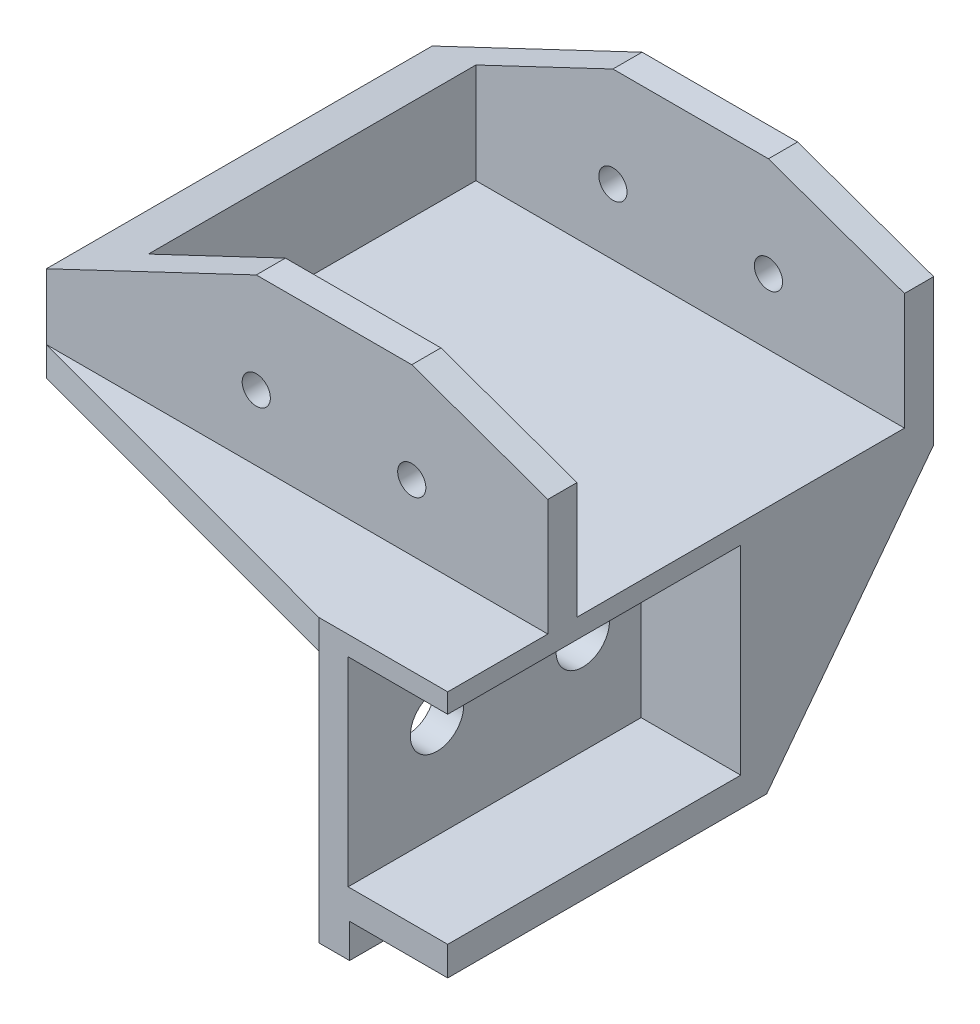
SolidWorks part; units mm, degrees
ref_plane "前视基准面" through (0, 0, 0) normal (0, 0, 1) x (1, 0, 0)
ref_plane "上视基准面" through (0, 0, 0) normal (0, 1, 0) x (1, 0, 0)
ref_plane "右视基准面" through (0, 0, 0) normal (1, 0, 0) x (0, 0, -1)
sketch "草图1" plane through (0, 0, 0) normal (0, 0, 1) x (1, 0, 0)
  line L0 (0, 0) -> (-103.2, 0)
  line L1 (-103.2, 0) -> (-103.2, 20)
  line L2 (-103.2, 20) -> (0, 20)
  line L3 (0, 20) -> (0, 0)
  dimension "D1" = 103.2
  dimension "D2" = 20
extrude "凸台-拉伸1" add sketch "草图1" along normal blind 39.7
sketch "草图2" plane through (0, 20, 0) normal (0, 1, 0) x (1, 0, 0)
  line L0 (-51.6, 0) -> (-51.6, -39.7) construction
  line L2 (-99.2, -19.85) -> (-72.6862, -19.85) construction
  line L5 (-95.7, -3) -> (-7.5, -3)
  line L6 (-95.7, -3) -> (-95.7, -36.7)
  line L7 (-95.7, -36.7) -> (-7.5, -36.7)
  line L8 (-7.5, -3) -> (-7.5, -36.7)
  dimension "D1" = 88.2
  dimension "D2" = 33.7
extrude "切除-拉伸1" cut sketch "草图2" against normal offset from surface (17 mm away) 3 up to face at (-51.6, 0, 19.85)
sketch "草图3" plane through (0, 0, 0) normal (0, -1, 0) x (1, 0, 0)
  line L6 (-51.6, 39.7) -> (-51.6, -13.7739) construction
  line L11 (-103.2, 0) -> (0, 0) construction
  line L12 (-64.85, 0) -> (-38.35, 0)
  line L15 (-64.85, 0) -> (-64.85, 50)
  line L16 (-64.85, 50) -> (-38.35, 50)
  line L17 (-38.35, 50) -> (-38.35, 0)
  point P11 (-51.6, 0)
  dimension "D1" = 50
  dimension "D2" = 13.25
extrude "凸台-拉伸2" add sketch "草图3" along normal blind 29 from offset 3 offset against normal yes
sketch "草图21" plane through (0, 0, 50) normal (0, 0, 1) x (1, 0, 0)
  line L0 (-7.5, 3) -> (-95.7, 3) construction
  line L1 (-7.5, 3) -> (-95.7, 3) construction
  line L2 (-98.033, -9.25) -> (-9.0097, -9.25) construction
  line L3 (-51.6, -26) -> (-51.6, 30.6239) construction
  line L4 (-61.85, 1) -> (-41.35, 1)
  line L5 (-61.85, 1) -> (-61.85, -19.5)
  line L6 (-61.85, -19.5) -> (-41.35, -19.5)
  line L7 (-41.35, 1) -> (-41.35, -19.5)
  dimension "D1" = 12.25
  dimension "D2" = 20.5
  dimension "D3" = 20.5
extrude "切除-拉伸11" cut sketch "草图21" against normal offset from surface (30.15 mm away) 19.85 up to face at (-51.6, -1.5, 0)
sketch "草图22" plane through (0, -26, 0) normal (0, -1, 0) x (1, 0, 0)
  line L1 (-61.7, 50) -> (-41.5, 50)
  line L2 (-41.5, 50) -> (-41.5, 0)
  line L3 (-64.85, 0) -> (-38.35, 0) construction
  line L4 (-41.5, 0) -> (-61.7, 0)
  line L5 (-61.7, 0) -> (-61.7, 50)
  line L6 (-38.35, 50) -> (-64.85, 50) construction
  dimension "D1" = 0
extrude "切除-拉伸12" cut sketch "草图22" against normal offset from surface (3.5 mm away) 3 up to face at (-51.6, -19.5, 34.925)
sketch "草图24" plane through (-38.35, 0, 0) normal (1, 0, 0) x (0, 0, -1)
  line L0 (0, 0) -> (0, -26)
  line L1 (0, -26) -> (-19.85, -26)
  line L2 (0, -26) -> (-50, -26) construction
  line L3 (-19.85, -26) -> (0, 0)
  line L4 (-19.85, -19.5) -> (-19.85, 1) construction
  line L5 (-19.85, -19.5) -> (-19.85, 1) construction
extrude "切除-拉伸14" cut sketch "草图24" against normal through all
sketch "草图25" plane through (0, 0, 0) normal (0, -1, 0) x (1, 0, 0)
  line L0 (-38.35, 39.7) -> (-38.35, 50)
  line L1 (-38.35, 50) -> (0, 39.7)
  line L2 (-51.6, 50) -> (-51.6, 41.294) construction
  line L4 (-38.35, 39.7) -> (0, 39.7)
  line L5 (-64.85, 39.7) -> (-103.2, 39.7)
  line L6 (-64.85, 50) -> (-103.2, 39.7)
  line L7 (-64.85, 39.7) -> (-64.85, 50)
extrude "凸台-拉伸4" add sketch "草图25" against normal up to surface (3 mm away) up to face at (-51.6, 3, 44.85)
hole_wizard "M2.5 间隙孔1" positions "草图26" profile "草图27" hole size "M2.5" standard "ISO" end condition through all
sketch "草图26" plane through (0, 0, 0) normal (0, 0, -1) x (-1, 0, 0)
  line L0 (-2.4764, 3) -> (110.5641, 3) construction
  line L2 (38.35, 0) -> (0, 0) construction
  line L3 (51.6, 0) -> (51.6, 22.298) construction
  point P8 (37.6, 9.75)
  point P10 (21.6, 9.75)
  point P23 (65.6, 9.75)
  point P24 (81.6, 9.75)
  dimension "D1" = 3
  dimension "D2" = 14
  dimension "D3" = 16
  dimension "D4" = 6.75
  dimension "D5" = 6.75
sketch "草图27" plane through (-81.6, 9.75, 0) normal (1, 0, 0) x (0, 1, 0)
  line L0 (0, 0) -> (0, 50)
  line L1 (0, 50) -> (1.45, 50)
  line L2 (1.45, 50) -> (1.45, 0.025)
  line L3 (1.45, 0.025) -> (1.475, 0)
  line L5 (1.475, 0) -> (0, 0)
  line L6 (-1.45, 0.025) -> (-1.475, 0) construction
  line L11 (0, -6.35) -> (0, 107.95) construction
  dimension "通孔孔直径" = 2.9
  dimension "通孔孔深度" = 50
  dimension "近端锥形沉头孔直径" = 2.95
  dimension "近端锥形沉头孔角度" = 90
hole_wizard "M5 间隙孔2" positions "草图34" profile "草图33" hole size "M5" standard "ISO" end condition through all
sketch "草图34" plane through (-38.35, 0, 0) normal (1, 0, 0) x (0, 0, -1)
  line L2 (-43.9538, -9.25) -> (-19.6706, -9.25) construction
  line L5 (-19.85, 0.85) -> (-19.85, -19.35) construction
  line L7 (-19.85, 1) -> (-50, 1) construction
  point P10 (-25.85, -9.25)
  point P21 (-40.85, -9.25)
  dimension "D1" = 6
  dimension "D2" = 15
sketch "草图33" plane through (-38.35, -9.25, 40.85) normal (0, 1, 0) x (0, 0, -1)
  line L0 (0, 0) -> (0, 64.85)
  line L1 (0, 64.85) -> (2.75, 64.85)
  line L2 (2.75, 64.85) -> (2.75, 0.025)
  line L3 (2.75, 0.025) -> (2.775, 0)
  line L5 (2.775, 0) -> (0, 0)
  line L6 (-2.75, 0.025) -> (-2.775, 0) construction
  line L11 (0, -6.35) -> (0, 107.95) construction
  dimension "通孔孔直径" = 5.5
  dimension "通孔孔深度" = 64.85
  dimension "近端锥形沉头孔直径" = 5.55
  dimension "近端锥形沉头孔角度" = 90
sketch "草图35" plane through (0, 0, 0) normal (0, 0, -1) x (-1, 0, 0)
  line L0 (21.6, 9.75) -> (37.6, 9.75) construction
  line L1 (21.6, 9.75) -> (21.6, 21.6918) construction
  line L2 (37.6, 9.75) -> (37.6, 21.6918) construction
  line L3 (0, 9.75) -> (21.6, 20)
  line L4 (0, 0) -> (0, 20) construction
  line L5 (21.6, 20) -> (0, 20)
  line L6 (0, 20) -> (0, 9.75)
  line L7 (0, 20) -> (103.2, 20) construction
  line L8 (51.6, 0) -> (51.6, 24.4852) construction
  line L10 (37.6, 20) -> (51.6, 15)
  line L11 (51.6, 15) -> (51.6, 20)
  line L12 (65.6, 20) -> (37.6, 20)
  line L13 (81.6, 20) -> (103.2, 20)
  line L14 (103.2, 9.75) -> (81.6, 20)
  line L15 (103.2, 20) -> (103.2, 9.75)
  line L16 (65.6, 20) -> (51.6, 15)
  line M17 (103.2, 0) -> (103.2, 20)
  line M18 (103.2, 20) -> (0, 20)
  dimension "D1" = 5
extrude "切除-拉伸19" cut sketch "草图35" against normal through all contours L14 M17 M18 | L6 L3 L5 | L16 L12 L10 region at (-96, 16.5833, 0)
ref_plane "基准面1" through (-51.6, 0, 0) normal (-1, 0, 0) x (0, 0, 1)
sketch "草图36" plane through (-51.6, 0, 0) normal (-1, 0, 0) x (0, 0, 1)
  line L1 (0, 20) -> (50, 20)
  line L2 (0, 20) -> (0, -26)
  line L3 (0, -26) -> (50, -26)
  line L4 (50, 20) -> (50, -26)
extrude "切除-拉伸20" cut sketch "草图36" against normal up to surface (51.6 mm away) up to face at (0, 4.5, 23.82)
ref_plane "Plane1" through (0, -9.25, 0) normal (0, 1, 0) x (1, 0, 0)
